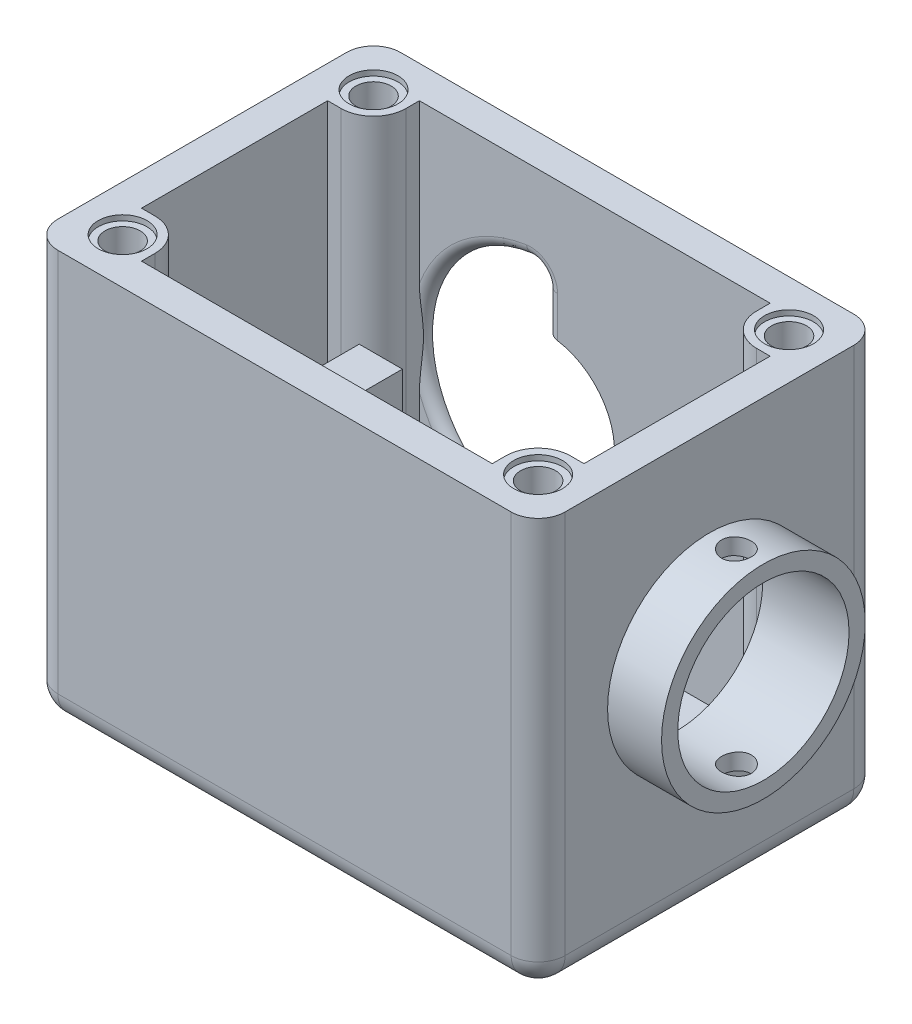
SolidWorks part; units mm, degrees
other "Markup1"
sketch "Sketch54" plane through (-29.5417, 76.2, -31.75) normal (-0.3541, 0.9345, -0.0352) x (0.0745, -0.0093, -0.9972)
ref_plane "Front Plane" through (0, 0, 0) normal (0, 0, 1) x (1, 0, 0)
ref_plane "Top Plane" through (0, 0, 0) normal (0, 1, 0) x (1, 0, 0)
ref_plane "Right Plane" through (0, 0, 0) normal (1, 0, 0) x (0, 0, -1)
sketch "Sketch1" plane through (0, 0, 0) normal (0, 1, 0) x (1, 0, 0)
  line L1 (0, 31.75) -> (94, 31.75)
  line L2 (0, 31.75) -> (0, -31.75)
  line L3 (0, -31.75) -> (94, -31.75)
  line L4 (94, 31.75) -> (94, -31.75)
  point P4 (0, 0)
extrude "Boss-Extrude1" add sketch "Sketch1" along normal blind 76.2
sketch "Sketch2" plane through (0, 76.2, 0) normal (0, 1, 0) x (1, 0, 0)
  line L0 (0, 31.75) -> (0, -31.75) construction
  line L1 (6, 25.75) -> (88, 25.75)
  line L2 (6, 25.75) -> (6, -25.75)
  line L3 (6, -25.75) -> (88, -25.75)
  line L4 (88, 25.75) -> (88, -25.75)
  line L5 (94, 31.75) -> (0, 31.75) construction
  line L6 (0, -31.75) -> (94, -31.75) construction
  line L7 (94, -31.75) -> (94, 31.75) construction
  dimension "D1" = 6
  dimension "D2" = 6
  dimension "D3" = 6
  dimension "D4" = 6
extrude "Cut-Extrude1" cut sketch "Sketch2" against normal blind 70.2
sketch "Sketch3" plane through (0, 0, 31.75) normal (0, 0, 1) x (1, 0, 0)
  line L0 (340.2875, 38.1) -> (-29.5417, 38.1) construction
  line L1 (94, 76.2) -> (94, 0) construction
  circle A1 centre (55.9, 38.1) radius 31.95
  dimension "D1" = 38.1
sketch "Sketch7" plane through (0, 0, -31.75) normal (0, 0, -1) x (-1, 0, 0)
  line L0 (-340.2875, 38.1) -> (29.5417, 38.1) construction
  line L1 (0, 76.2) -> (0, 0) construction
  circle A0 centre (-38.1, 38.1) radius 31.95
  dimension "D1" = 38.1
extrude "Cut-Extrude4" cut sketch "Sketch7" against normal blind 4
sketch "Sketch8" plane through (0, 0, -25.75) normal (0, 0, 1) x (1, 0, 0)
  line L0 (340.2875, 38.1) -> (-29.5417, 38.1) construction
  line L1 (0, 76.2) -> (0, 0) construction
  circle A0 centre (38.1, 38.1) radius 12.55
  dimension "D1" = 38.1
extrude "Cut-Extrude5" cut sketch "Sketch8" against normal blind 2
sketch "Sketch11" plane through (0, 0, 25.75) normal (0, 0, -1) x (-1, 0, 0)
  line L1 (-66, 48.2) -> (-25.5, 48.2) construction
  line L2 (-66, 48.2) -> (-66, 28) construction
  line L3 (-66, 28) -> (-25.5, 28) construction
  line L4 (-25.5, 48.2) -> (-25.5, 28) construction
  dimension "D1" = 10.1
  dimension "D2" = 20.2
  dimension "D3" = 10.1
  dimension "D4" = 40.5
sketch "Sketch14" plane through (0, 6, 0) normal (0, 1, 0) x (1, 0, 0)
  line L6 (165.1, 43.154) -> (165.1, -44.7121) construction
  line L11 (6, 25.75) -> (6, -25.75) construction
  line L12 (20, 9.1) -> (28, 9.1)
  line L13 (20, 9.1) -> (20, -0.2)
  line L14 (20, -0.2) -> (28, -0.2)
  line L15 (28, 9.1) -> (28, -0.2)
  line L16 (76.5, 9.1) -> (68.5, 9.1)
  line L17 (76.5, 9.1) -> (76.5, -0.2)
  line L18 (76.5, -0.2) -> (68.5, -0.2)
  line L19 (68.5, 9.1) -> (68.5, -0.2)
  line L20 (88, 25.75) -> (6, 25.75) construction
  point P26 (24, 9.1)
  dimension "D4" = 40.5
  dimension "D5" = 14
  dimension "D6" = 16.65
extrude "Boss-Extrude2" add sketch "Sketch14" along normal blind 42.2
ref_plane "Plane2" through (0, 28, 0) normal (0, 1, 0) x (1, 0, 0)
sketch "Sketch15" plane through (0, 28, 0) normal (0, 1, 0) x (1, 0, 0)
  line L5 (28, 9.1) -> (68.5, 9.1)
  line L6 (28, 9.1) -> (28, -0.2)
  line L8 (68.5, 9.1) -> (68.5, -0.2)
  line L9 (20, -0.2) -> (28, -0.2)
  line L10 (20, -0.2) -> (20, -11.2)
  line L11 (20, -11.2) -> (76.5, -11.2)
  line L12 (76.5, -0.2) -> (76.5, -11.2)
  line L14 (76.5, -0.2) -> (76.5, 9.1) construction
  line L15 (20, 9.1) -> (20, -0.2) construction
  line L16 (68.5, -0.2) -> (76.5, -0.2)
extrude "Boss-Extrude3" add sketch "Sketch15" against normal blind 22
sketch3d "3DSketch2"
  line L0 (6, 6, 0) -> (344.0999, 6, 0) construction
  line L1 (6, 6, -25.75) -> (6, 6, 25.75) construction
ref_plane "Plane3" through (0, 0, 0) normal (0, 0, 1) x (1, 0, 0)
sketch "Sketch17" plane through (0, 28, 0) normal (0, 1, 0) x (1, 0, 0)
  line L0 (23, 9.1) -> (23, -11.2) construction
  line L2 (73.5, 9.1) -> (73.5, -11.2) construction
  line L5 (20, -5.7) -> (76.5, -5.7) construction
  line L6 (20, -0.2) -> (20, -11.2) construction
  line L7 (76.5, -11.2) -> (76.5, -0.2) construction
  circle A0 centre (23, -5.7) radius 1.5
  circle A1 centre (73.5, -5.7) radius 1.5
  dimension "D3" = 3
  dimension "D4" = 3
hole_wizard "Ø1.0mm Dowel Hole1" positions "Sketch23" profile "Sketch24" hole size "Ø1.0" standard "ANSI Metric"
sketch "Sketch23" plane through (0, 28, 0) normal (0, 1, 0) x (1, 0, 0)
  point P0 (23, -5.7)
  point P3 (73.5, -5.7)
sketch "Sketch24" plane through (23, 28, 5.7) normal (1, 0, 0) x (0, 0, 1)
  line L0 (0, 0) -> (0, 11.5215)
  line L1 (0, 11.5215) -> (1.7, 10.5)
  line L2 (1.7, 10.5) -> (1.7, 0)
  line L5 (1.7, 0) -> (0, 0)
  line L10 (0, 11.5215) -> (-1.7, 10.5) construction
  line L11 (0, -6.35) -> (0, 107.95) construction
  dimension "Hole Dia." = 3.4
  dimension "Hole Depth" = 10.5
  dimension "Drill Angle" = 118
sketch "Sketch25" plane through (0, 0, -9.1) normal (0, 0, -1) x (-1, 0, 0)
  line L0 (-72.5, 48.2) -> (-72.5, 10.586) construction
  line L1 (-76.5, 48.2) -> (-68.5, 48.2) construction
  line L3 (-24, 48.2) -> (-24, 23.4435) construction
  line L4 (-28, 48.2) -> (-20, 48.2) construction
  line L5 (-76.5, 42.43) -> (-68.5, 42.43) construction
  line L6 (-76.5, 48.2) -> (-76.5, 6) construction
  line L7 (-68.5, 48.2) -> (-68.5, 28) construction
  line L8 (-76.5, 33.72) -> (-68.5, 33.72) construction
  line L9 (-20, 33.72) -> (-28, 33.72) construction
  line L10 (-20, 48.2) -> (-20, 6) construction
  line L11 (-28, 48.2) -> (-28, 28) construction
  line L12 (-28, 42.43) -> (-20, 42.43) construction
  circle A0 centre (-72.5, 42.43) radius 2
  circle A1 centre (-72.5, 33.72) radius 2
  circle A2 centre (-24, 33.72) radius 2
  circle A3 centre (-24, 42.43) radius 2
  dimension "D1" = 5.77
  dimension "D2" = 14.48
hole_wizard "Ø1.0mm Dowel Hole2" positions "Sketch26" profile "Sketch27" hole size "Ø1.0" standard "ANSI Metric"
sketch "Sketch26" plane through (0, 0, -9.1) normal (0, 0, -1) x (-1, 0, 0)
  point P0 (-72.5, 42.43)
  point P3 (-72.5, 33.72)
  point P6 (-24, 42.43)
  point P9 (-24, 33.72)
sketch "Sketch27" plane through (72.5, 42.43, -9.1) normal (1, 0, 0) x (0, 1, 0)
  line L0 (0, 0) -> (0, 6.5017)
  line L1 (0, 6.5017) -> (2, 5.3)
  line L2 (2, 5.3) -> (2, 0)
  line L5 (2, 0) -> (0, 0)
  line L10 (0, 6.5017) -> (-2, 5.3) construction
  line L11 (0, -6.35) -> (0, 107.95) construction
  dimension "Hole Dia." = 4
  dimension "Hole Depth" = 5.3
  dimension "Drill Angle" = 118
fillet "Fillet1" radius 5 8 edges at (0, 0, 0) (47, 0, 31.75) (0, 38.1, 31.75) (0, 38.1, -31.75) (47, 0, -31.75) (94, 0, 0) (94, 38.1, 31.75) (94, 38.1, -31.75)
sketch "Sketch44" plane through (0, 76.2, 0) normal (0, 1, 0) x (1, 0, 0)
  line L0 (8.5, 33.9856) -> (8.5, -37.2084) construction
  line L1 (-4.0359, -23.25) -> (97.4564, -23.25) construction
  line L2 (-4.0359, 23.25) -> (97.4564, 23.25) construction
  line L3 (85.5, -34.1183) -> (85.5, 34.8738) construction
  line L4 (6, 25.75) -> (6, -25.75) construction
  line L5 (88, -25.75) -> (88, 25.75) construction
  line L6 (88, 25.75) -> (6, 25.75) construction
  line L7 (6, -25.75) -> (88, -25.75) construction
  line L8 (8.5, 17.25) -> (6, 17.25)
  line L10 (14.5, 23.25) -> (14.5, 25.75)
  line L11 (88, 25.75) -> (6, 25.75) construction
  line L12 (6, 25.75) -> (6, -25.75) construction
  line L13 (6, 17.25) -> (6, 25.75)
  line L14 (6, 25.75) -> (14.5, 25.75)
  line L15 (8.5, -17.25) -> (6, -17.25)
  line L16 (6, -17.25) -> (6, -25.75)
  line L17 (6, -25.75) -> (14.5, -25.75)
  line L18 (14.5, -25.75) -> (14.5, -23.25)
  line L19 (79.5, -23.25) -> (79.5, -25.75)
  line L20 (79.5, -25.75) -> (88, -25.75)
  line L21 (88, -25.75) -> (88, -17.25)
  line L22 (88, -17.25) -> (85.5, -17.25)
  line L23 (79.5, 23.25) -> (79.5, 25.75)
  line L24 (79.5, 25.75) -> (88, 25.75)
  line L25 (88, 25.75) -> (88, 17.25)
  line L26 (88, 17.25) -> (85.5, 17.25)
  arc A0 (8.5, 17.25) -> (14.5, 23.25) centre (8.5, 23.25) ccw
  arc A1 (14.5, -23.25) -> (8.5, -17.25) centre (8.5, -23.25) ccw
  arc A2 (85.5, -17.25) -> (79.5, -23.25) centre (85.5, -23.25) ccw
  arc A3 (79.5, 23.25) -> (85.5, 17.25) centre (85.5, 23.25) ccw
  dimension "D1" = 2.5
  dimension "D2" = 2.5
  dimension "D3" = 2.5
  dimension "D4" = 2.5
extrude "Boss-Extrude4" add sketch "Sketch44" against normal up to surface (70.2 mm away) up to face at (48.25, 6, 1.05)
sketch "Sketch45" plane through (0, 76.2, 0) normal (0, 1, 0) x (1, 0, 0)
  line L0 (-5.0131, 0) -> (101.0279, 0) construction
  circle A0 centre (8.5, 23.25) radius 3.4
  circle A1 centre (85.5, 23.25) radius 3.4
  circle A2 centre (85.5, -23.25) radius 3.4
  circle A3 centre (8.5, -23.25) radius 3.4
hole_wizard "CBORE for M5 Hex Head Bolt1" positions "Sketch48" profile "Sketch47" counterbore size "M5" standard "ANSI Metric"
sketch "Sketch48" plane through (0, 76.2, 0) normal (0, 1, 0) x (1, 0, 0)
  point P0 (8.5, 23.25)
  point P4 (8.5, -23.25)
  point P7 (85.5, -23.25)
  point P10 (85.5, 23.25)
sketch "Sketch47" plane through (8.5, 76.2, -23.25) normal (1, 0, 0) x (0, 0, 1)
  line L0 (0, 0) -> (0, 12.7028)
  line L1 (0, 12.7028) -> (3.25, 10.75)
  line L2 (3.25, 10.75) -> (3.25, 1)
  line L3 (3.25, 1) -> (4.525, 1)
  line L4 (4.525, 1) -> (4.525, 0)
  line L5 (4.525, 0) -> (0, 0)
  line L10 (0, 12.7028) -> (-3.25, 10.75) construction
  line L11 (0, -6.35) -> (0, 107.95) construction
  dimension "Hole Dia." = 6.5
  dimension "Hole Depth" = 10.75
  dimension "C'Bore Dia." = 9.05
  dimension "C'Bore Depth" = 1
  dimension "Drill Angle" = 118
sketch "Sketch49" plane through (94, 0, 0) normal (1, 0, 0) x (0, 0, -1)
  line L0 (0, 76.2) -> (0, -3.4439) construction
  line L1 (-26.75, 76.2) -> (26.75, 76.2) construction
  line L2 (-35.746, 40.6) -> (38.1435, 40.6) construction
  circle A0 centre (0, 40.6) radius 15.875
extrude "Cut-Extrude7" cut sketch "Sketch49" against normal up to surface (6 mm away) up to face at (88, 41.1, 0)
sketch "Sketch51" plane through (94, 0, 0) normal (1, 0, 0) x (0, 0, -1)
  circle A0 centre (0, 40.6) radius 15.875
  circle A1 centre (0, 40.6) radius 18.875
extrude "Boss-Extrude5" add sketch "Sketch51" along normal blind 10
ref_plane "Plane4" through (0, 59.475, 0) normal (0, 1, 0) x (-1, 0, 0)
sketch "Sketch52" plane through (0, 59.475, 0) normal (0, 1, 0) x (-1, 0, 0)
  line L0 (-104, 0) -> (-91.3804, 0) construction
  line L1 (-104, 18.875) -> (-104, -18.875) construction
  line L2 (-88, -5.5815) -> (-88, 5.2767) construction
  line L3 (-88, 17.25) -> (-88, -17.25) construction
  line L4 (-88, 17.25) -> (-88, -17.25) construction
  circle A0 centre (-99, 0) radius 2.75
  dimension "D1" = 5
  dimension "D2" = 11
extrude "Cut-Extrude8" cut sketch "Sketch52" against normal through all
sketch "Sketch53" plane through (0, 0, -27.75) normal (0, 0, -1) x (-1, 0, 0)
  line L0 (-38.1, 61.27) -> (-38.1, 14.93)
  arc A0 (-38.1, 14.93) -> (-38.1, 61.27) centre (-38.1, 38.1) ccw
extrude "Cut-Extrude9" cut sketch "Sketch53" against normal up to surface (2 mm away) up to face at (50.65, 38.1, -25.75)
fillet "Fillet2" radius 3 2 edges at (38.1, 14.93, -26.75) (38.1, 61.27, -26.75)
fillet "Fillet3" radius 2 5 edges at (38.1, 54.3478, -25.75) (37.0572, 60.3193, -25.75) (38.1, 21.8522, -25.75) (37.0572, 15.8807, -25.75) (14.93, 38.1, -25.75)
